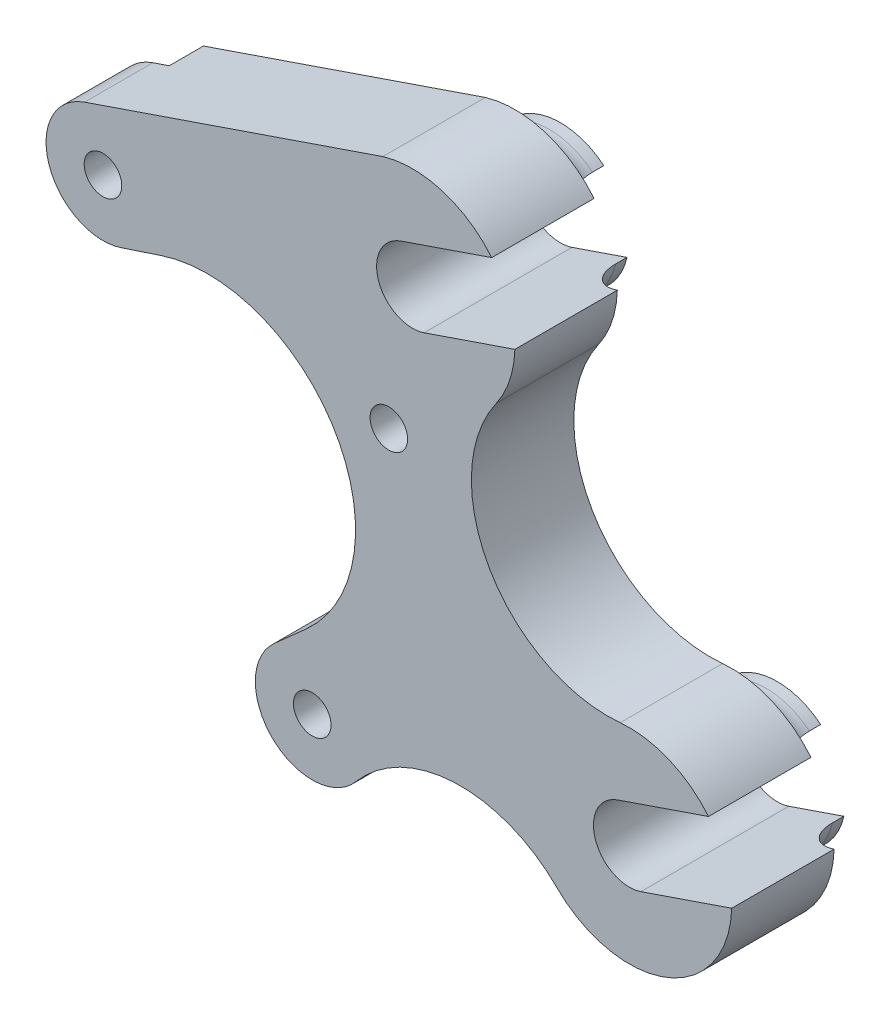
SolidWorks part; units mm, degrees
ref_plane "Front Plane" through (0, 0, 0) normal (0, 0, 1) x (1, 0, 0)
ref_plane "Top Plane" through (0, 0, 0) normal (0, 1, 0) x (1, 0, 0)
ref_plane "Right Plane" through (0, 0, 0) normal (1, 0, 0) x (0, 0, -1)
sketch "Sketch1" plane through (0, 0, 0) normal (0, 0, 1) x (1, 0, 0)
  line L0 (18, 21) -> (37.0525, -11.9999) construction
  line L1 (15.9217, 9.1924) -> (-9.1924, 15.9217) construction
  line L2 (-9.1924, 15.9217) -> (-15.9217, -9.1924) construction
  line L3 (-15.9217, -9.1924) -> (9.1924, -15.9217) construction
  line L4 (9.1924, -15.9217) -> (15.9217, 9.1924) construction
  line L5 (0, 0) -> (50.7667, 0) construction
  line L6 (0, 0) -> (-9.1924, 15.9217) construction
  line L7 (-4.0727, 12.3456) -> (-7.626, 11.1734)
  line L8 (8.6552, -9.6998) -> (5.8634, -12.191)
  line L9 (0, 0) -> (9.1924, -15.9217) construction
  line L10 (15.3981, 29.6157) -> (-10.8103, 20.6527)
  line L11 (16.9807, 23.9805) -> (24.9578, 26.7086)
  line L12 (19.0193, 18.0195) -> (26.9965, 20.7476)
  line L13 (36.0332, -9.0194) -> (44.0103, -6.2913)
  line L14 (38.0718, -14.9804) -> (46.049, -12.2523)
  arc A0 (8.6552, -9.6998) -> (-4.0727, 12.3456) centre (0, 0) ccw
  arc A1 (16.9807, 23.9805) -> (19.0193, 18.0195) centre (18, 21) ccw
  circle A2 centre (-9.1924, 15.9217) radius 1.65
  circle A3 centre (15.9217, 9.1924) radius 1.65
  circle A4 centre (9.1924, -15.9217) radius 1.65
  arc A5 (25.3607, 15.8211) -> (26.9965, 20.7476) centre (18, 21) ccw
  arc A6 (36.0332, -9.0194) -> (38.0718, -14.9804) centre (37.0525, -11.9999) ccw
  arc A7 (-10.8103, 20.6527) -> (-7.626, 11.1734) centre (-9.1924, 15.9217) ccw
  arc A8 (44.0103, -6.2913) -> (36.2478, -3.0359) centre (37.0525, -11.9999) ccw
  arc A9 (30.6913, -18.3666) -> (46.049, -12.2523) centre (37.0525, -11.9999) ccw
  arc A10 (5.8634, -12.191) -> (13.021, -19.1375) centre (9.1924, -15.9217) ccw
  arc A11 (30.6913, -18.3666) -> (13.021, -19.1375) centre (22.2097, -26.8556) ccw
  arc A12 (25.3607, 15.8211) -> (36.2478, -3.0359) centre (35.1749, 8.916) ccw
  arc A13 (24.9578, 26.7086) -> (15.3981, 29.6157) centre (18, 21) ccw
  dimension "D1" = 26
  dimension "D2" = 3.3
  dimension "D3" = 6.3
  dimension "D9" = 5
  dimension "D10" = 9
  dimension "D11" = 12
  dimension "D12" = 12
  dimension "D4" = 21
  dimension "D5" = 38.105
  dimension "D6" = 60
  dimension "D7" = 18
  dimension "D8" = 15
extrude "Boss-Extrude1" add sketch "Sketch1" along normal blind 9
sketch "Sketch2" plane through (0, 0, 0) normal (0, 0, -1) x (-1, 0, 0)
  line L0 (-9.1924, -15.9217) -> (-15.9217, 9.1924) construction
  line L1 (10.7961, 21.5278) -> (-20.1136, 13.2456)
  line L2 (-21.5278, 10.7961) -> (-13.2456, -20.1136)
  line L5 (-20.1136, 13.2456) -> (-21.5278, 10.7961)
  line L6 (23.2164, 14.3569) -> (10.7961, 21.5278)
  line L8 (-13.2456, -20.1136) -> (8.7791, -32.8295)
  line L9 (23.2164, 14.3569) -> (8.7791, -32.8295)
  line L11 (20.7057, -7.7281) -> (13.9247, 17.5792) [skipped]
  line L12 (-7.7281, -20.7057) -> (17.5792, -13.9247) [skipped]
  circle A0 centre (0, 0) radius 18 construction
  circle A1 centre (0, 0) radius 24.0416 construction
  circle A2 centre (-18, 21) radius 6 construction
  circle A3 centre (-18, 21) radius 3.15 construction
  point P2 (6.5153, 24.3153)
  point P3 (-22.0454, 12.7279)
  point P4 (-6.5153, -24.3153)
  point P5 (24.3153, -6.5153)
  dimension "D1" = 36
  dimension "D2" = 12
  dimension "D4" = 2
extrude "Cut-Extrude1" cut sketch "Sketch2" against normal offset from surface (3 mm away) 6 up to face at (17.5717, 9.1924, 9)
sketch "Sketch3" plane through (0, 0, 0) normal (0, 0, -1) x (-1, 0, 0)
  line L0 (-16.9807, 23.9805) -> (-21.8126, 25.633)
  line L1 (-16.9807, 23.9805) -> (-24.9578, 26.7086) construction
  line L2 (-19.0193, 18.0195) -> (-23.8512, 19.6719)
  line L3 (-38.0718, -14.9804) -> (-42.9037, -13.328)
  line L4 (-46.049, -12.2523) -> (-38.0718, -14.9804) construction
  line L5 (-36.0332, -9.0194) -> (-40.8651, -7.3669)
  line L6 (-36.0332, -9.0194) -> (-44.0103, -6.2913) construction
  arc A0 (-23.8512, 19.6719) -> (-21.8126, 25.633) centre (-18, 21) ccw
  arc A1 (-19.0193, 18.0195) -> (-16.9807, 23.9805) centre (-18, 21) ccw
  arc A2 (-38.0718, -14.9804) -> (-36.0332, -9.0194) centre (-37.0525, -11.9999) ccw
  arc A3 (-42.9037, -13.328) -> (-40.8651, -7.3669) centre (-37.0525, -11.9999) ccw
  dimension "D1" = 12
extrude "Boss-Extrude2" add sketch "Sketch3" along normal blind 4
fillet "Fillet1" radius 3 2 edges at (12.3228, 19.0585, 0)
